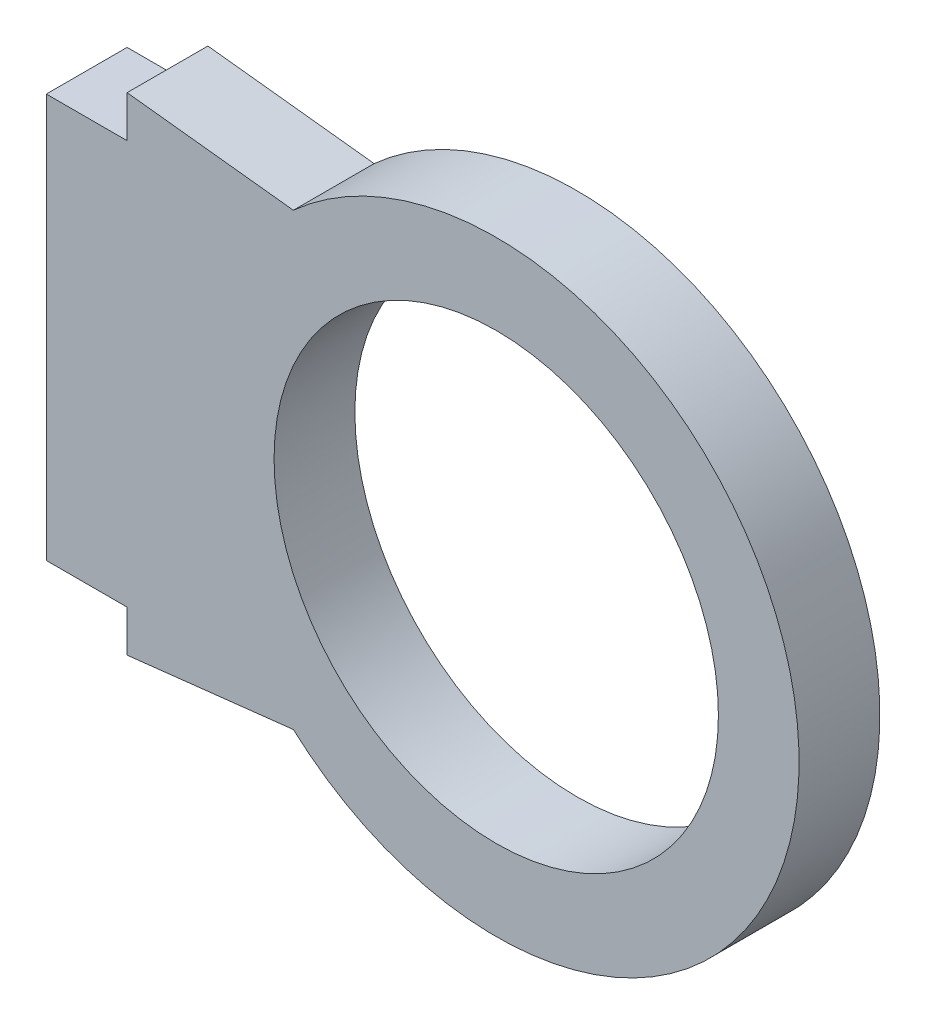
SolidWorks part; units mm, degrees
ref_plane "Alzado" through (0, 0, 0) normal (0, 0, 1) x (1, 0, 0)
ref_plane "Planta" through (0, 0, 0) normal (0, 1, 0) x (1, 0, 0)
ref_plane "Vista lateral" through (0, 0, 0) normal (1, 0, 0) x (0, 0, -1)
sketch "Croquis1" plane through (0, 0, 0) normal (0, 0, 1) x (1, 0, 0)
  line L0 (-2, 14.3781) -> (-2, -5.6219)
  line L1 (-2, -5.6219) -> (2, -5.6219)
  line L3 (2, 14.3781) -> (-2, 14.3781)
  line L4 (2, 14.3781) -> (2, 16.4374)
  line L5 (2, 16.4374) -> (20.2923, 14.3781)
  line L8 (2, -7.6812) -> (20.2923, -5.6219)
  line L9 (2, 16.4374) -> (2, 14.3781)
  line L10 (2, -7.6812) -> (2, -5.6219)
  arc A0 (20.26, -5.6219) -> (20.2923, 14.3781) centre (20.2761, 4.3781) ccw
  circle A2 centre (20.2761, 4.3781) radius 4.2
extrude "Saliente-Extruir1" add sketch "Croquis1" along normal blind 4 contours L8 A0 L5 L4 L3 L0 L1 L10 A2 region at (12.147, 4.3781, 0)
sketch "Croquis2" plane through (0, 0, 4) normal (0, 0, 1) x (1, 0, 0)
  line L0 (9.4285, 14.7305) -> (14.5854, 13.7917)
  line L1 (9.9502, -6.4948) -> (14.4253, -4.9368)
  circle A0 centre (20.2761, 4.3781) radius 11
  arc A1 (9.9502, -6.4948) -> (9.4285, 14.7305) centre (20.2761, 4.3781) ccw
  line M3 (2, -7.6812) -> (20.2923, -5.6219)
  arc M4 (20.2923, -5.6219) -> (20.2923, 14.3781) centre (20.2761, 4.3781) ccw
  line M5 (20.2923, 14.3781) -> (2, 16.4374)
  circle M11 centre (20.2761, 4.3781) radius 4.2
extrude "Saliente-Extruir2" add sketch "Croquis2" against normal blind 4 contours A1 A0 M3 M5 region at (34.8802, 4.3781, 4)
extrude "Cortar-Extruir1" cut sketch "Croquis2<3>" against normal blind 4 contours A0 M5 M3 M4 M11 region at (15.7436, 14.0755, 4)
sketch "Croquis2<3>" plane through (0, 0, 4) normal (0, 0, 1) x (1, 0, 0) same geometry as "Croquis2"
